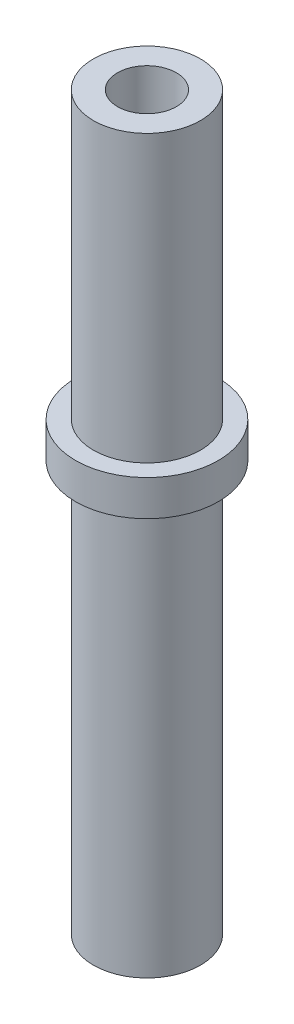
SolidWorks part; units mm, degrees
material "6061-T6 (SS)"
ref_plane "Front Plane" through (0, 0, 0) normal (0, 0, 1) x (1, 0, 0)
ref_plane "Top Plane" through (0, 0, 0) normal (0, 1, 0) x (1, 0, 0)
ref_plane "Right Plane" through (0, 0, 0) normal (1, 0, 0) x (0, 0, -1)
sketch "Sketch1" plane through (0, 0, 0) normal (0, 1, 0) x (1, 0, 0)
  circle A0 centre (0, 0) radius 3
  circle A1 centre (0, 0) radius 2 construction
  dimension "D1" = 6
  dimension "D2" = 4
extrude "Boss-Extrude1" add sketch "Sketch1" along normal blind 20.5 and the other way blind 20.5
sketch "Sketch2" plane through (0, 20.5, 0) normal (0, 1, 0) x (1, 0, 0)
  point P0 (0, 0)
hole_wizard "M4x0.7 Tapped Hole1" positions "Sketch4" profile "Sketch5" tap size "M4x0.7" standard "ANSI Metric"
sketch "Sketch4" plane through (0, 20.5, 0) normal (0, 1, 0) x (1, 0, 0)
  point P0 (0, 0)
sketch "Sketch5" plane through (0, 20.5, 0) normal (1, 0, 0) x (0, 0, 1)
  line L0 (0, 0) -> (0, 8.9914)
  line L1 (0, 8.9914) -> (1.65, 8)
  line L2 (1.65, 8) -> (1.65, 0)
  line L5 (1.65, 0) -> (0, 0)
  line L10 (0, 8.9914) -> (-1.65, 8) construction
  line L11 (0, -6.35) -> (0, 107.95) construction
  dimension "Tap Drill Dia." = 3.3
  dimension "Tap Drill Depth" = 8
  dimension "Drill Angle" = 118
cosmetic thread "Hole Thread1" parameters "D1"=8, "D2"=4
ref_plane "Plane1" through (0, 2.5, 0) normal (0, 1, 0) x (1, 0, 0)
sketch "Sketch6" plane through (0, 2.5, 0) normal (0, 1, 0) x (1, 0, 0)
  circle A0 centre (0, 0) radius 4
  dimension "D1" = 8
extrude "Boss-Extrude2" add sketch "Sketch6" along normal blind 2
mirror "Mirror1" about plane through (0, 0, 0) normal (0, 1, 0) of "M4x0.7 Tapped Hole1"
